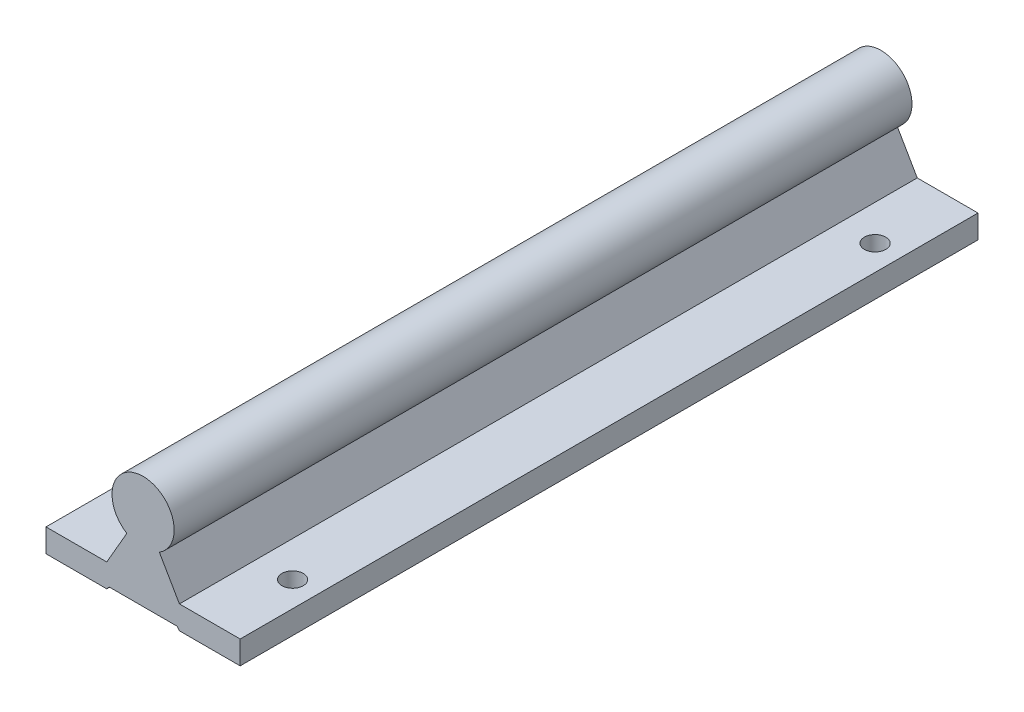
SolidWorks part; units mm, degrees
ref_plane "Спереди" through (0, 0, 0) normal (0, 0, 1) x (1, 0, 0)
ref_plane "Сверху" through (0, 0, 0) normal (0, 1, 0) x (1, 0, 0)
ref_plane "Справа" through (0, 0, 0) normal (1, 0, 0) x (0, 0, -1)
sketch "Эскиз2" plane through (0, 0, 0) normal (0, 0, 1) x (1, 0, 0)
  line L0 (4.1819, -6.8199) -> (9.355, -15.7799)
  line L1 (9.355, -15.7799) -> (25, -15.7799)
  line L2 (25, -15.7799) -> (25, -21.7799)
  line L3 (25, -21.7799) -> (9.355, -21.7799)
  line L4 (9.355, -21.7799) -> (8.7481, -21.0514)
  line L5 (8.7481, -21.0514) -> (-8.7481, -21.0514)
  line L6 (0, 0) -> (0, -47.3153) construction
  line L7 (-9.355, -21.7799) -> (-8.7481, -21.0514)
  line L8 (-25, -21.7799) -> (-9.355, -21.7799)
  line L9 (-25, -15.7799) -> (-25, -21.7799)
  line L10 (-9.355, -15.7799) -> (-25, -15.7799)
  line L11 (-4.1819, -6.8199) -> (-9.355, -15.7799)
  circle A0 centre (0, 0) radius 8
  point P12 (0, -21.0514)
  dimension "D6" = 16
  dimension "D1" = 6
  dimension "D2" = 60
  dimension "D3" = 18.71
  dimension "D4" = 50
  dimension "D5" = 14.96
  dimension "D7" = 21.7799
extrude "Бобышка-Вытянуть2" add sketch "Эскиз2" along normal blind 190 contours A0
extrude "Бобышка-Вытянуть3" add sketch "Эскиз2<4>" along normal blind 190 contours A0 L6 L5 L4 L3 L2 L1 L0 | L6 A0 L11 L10 L9 L8 L7 L5 region at (10.2391, -16.7967, 0) region at (-10.2391, -16.7967, 0)
sketch "Эскиз2<4>" plane through (0, 0, 0) normal (0, 0, 1) x (1, 0, 0) same geometry as "Эскиз2"
sketch "Эскиз7" plane through (0, -15.7799, 0) normal (0, 1, 0) x (1, 0, 0)
  line L0 (0, -999.7956) -> (0, 51.3021) construction
  line L1 (-9.355, -190) -> (-25, -190) construction
  line L2 (-18.5, -170) -> (-25, -170) construction
  line L3 (-25, -190) -> (-25, 0) construction
  line L4 (18.5, -170) -> (25, -170) construction
  line L5 (25, -190) -> (25, 0) construction
  line L6 (18.5, -170) -> (18.5, 35.3486) construction
  line L8 (-18.5, -170) -> (-18.5, -49.837) construction
  line L11 (-25, -190) -> (-25, 0) construction
  line L12 (25, -190) -> (25, 0) construction
  circle A0 centre (-18.5, -170) radius 2.75
  circle A1 centre (18.5, -170) radius 2.75
  circle A2 centre (18.5, -20) radius 2.75
  circle A3 centre (-18.5, -20) radius 2.75
  point P7 (-17.1775, -190)
  dimension "D1" = 20
  dimension "D2" = 37
  dimension "D3" = 5.5
  dimension "D4" = 150
  dimension "D5" = 37
extrude "Вырез-Вытянуть1" cut sketch "Эскиз7" against normal through all contours A1 | A0 | A3 | A2
hole_wizard "Цековка для винта с внутренним шестигранником M51" positions "Эскиз13" profile "Эскиз12" counterbore size "M5" standard "Ansi Metric"
sketch "Эскиз13" plane through (0, -21.0514, 0) normal (0, -1, 0) x (-1, 0, 0)
  line L0 (-18.5, -170) -> (18.5, -170) construction
  line L2 (-18.5, -20) -> (18.5, -20) construction
  point P0 (0, -20)
  point P2 (0, -170)
sketch "Эскиз12" plane through (0, -21.0514, 20) normal (1, 0, 0) x (0, 0, -1)
  line L0 (0, 0) -> (0, 19.5923)
  line L1 (0, 19.5923) -> (2.65, 18)
  line L2 (2.65, 18) -> (2.65, 5)
  line L3 (2.65, 5) -> (5, 5)
  line L4 (5, 5) -> (5, 0)
  line L5 (5, 0) -> (0, 0)
  line L10 (0, 19.5923) -> (-2.65, 18) construction
  line L11 (0, -6.35) -> (0, 107.95) construction
  dimension "Диаметр отверстия" = 5.3
  dimension "Глубина отверстия" = 18
  dimension "Диаметр цековки" = 10
  dimension "Глубина цековки" = 5
  dimension "Угол заточки сверла" = 118
equation "\"D\"=4.86916"
